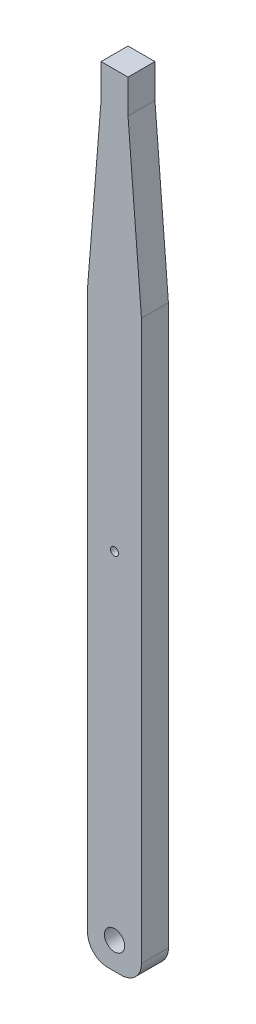
SolidWorks part; units mm, degrees
material "Custom Plastic"
ref_plane "Front Plane" through (0, 0, 0) normal (0, 0, 1) x (1, 0, 0)
ref_plane "Top Plane" through (0, 0, 0) normal (0, 1, 0) x (1, 0, 0)
ref_plane "Right Plane" through (0, 0, 0) normal (1, 0, 0) x (0, 0, -1)
sketch "Sketch1" plane through (0, 0, 0) normal (0, 0, 1) x (1, 0, 0)
  line L1 (4, -58) -> (-4, -58)
  line L2 (4, -58) -> (4, 58)
  line L3 (4, 58) -> (-4, 58)
  line L4 (-4, -58) -> (-4, 58)
  line L5 (4, -58) -> (-4, 58) construction
  line L6 (4, 58) -> (-4, -58) construction
  point P0 (0, 0)
  dimension "D1" = 116
  dimension "D2" = 8
extrude "Boss-Extrude1" add sketch "Sketch1" along normal blind 4
fillet "Fillet1" radius 3 2 edges at (4, -58, 2) (-4, -58, 2)
sketch "Sketch2" plane through (0, 0, 4) normal (0, 0, 1) x (1, 0, 0)
  line L0 (-4, 28) -> (-2, 53)
  line L1 (-4, 58) -> (-4, -55) construction
  line L2 (-2, 53) -> (-2, 58)
  line L3 (4, 58) -> (-4, 58) construction
  line L4 (-2, 58) -> (2, 58) construction
  line L5 (2, 58) -> (2, 53)
  line L6 (2, 53) -> (4, 28)
  line L7 (4, -55) -> (4, 58) construction
  line L8 (-4, 28) -> (-4, 58)
  line L9 (-4, 58) -> (-2, 58)
  line L10 (2, 58) -> (4, 58)
  line L11 (4, 58) -> (4, 28)
  point P4 (0, 58)
  dimension "D1" = 4
  dimension "D2" = 5
  dimension "D3" = 25
extrude "Cut-Extrude1" cut sketch "Sketch2" against normal up to surface (4 mm away) up to face at (0, -18.5404, 0)
hole_wizard "Ø1.0mm Dowel Hole1" positions "Sketch3" profile "Sketch5" hole size "Ø1.0" standard "ANSI Metric"
sketch "Sketch3" plane through (0, 0, 4) normal (0, 0, 1) x (1, 0, 0)
  line L0 (-1, -58) -> (1, -58) construction
  point P0 (0, -54)
  point P6 (0, -58)
  dimension "D1" = 4
sketch "Sketch5" plane through (0, -54, 4) normal (1, 0, 0) x (0, -1, 0)
  line L0 (0, 0) -> (0, 3.999)
  line L1 (0, 3.999) -> (1.5, 3.999)
  line L2 (1.5, 3.999) -> (1.5, 0)
  line L5 (1.5, 0) -> (0, 0)
  line L10 (0, 3.999) -> (-1.5, 3.999) construction
  line L11 (0, -6.35) -> (0, 107.95) construction
  dimension "Hole Dia." = 3
  dimension "Hole Depth" = 3.999
  dimension "Drill Angle" = 180
sketch "Sketch6" plane through (0, 0, 4) normal (0, 0, 1) x (1, 0, 0)
  circle A0 centre (0, -4) radius 0.6
  circle A1 centre (0, -54) radius 1.5 construction
  point P2 (0, 0)
  point P6 (0, 0)
  dimension "D1" = 50
  dimension "D2" = 1.2
extrude "Cut-Extrude2" cut sketch "Sketch6" against normal blind 10
